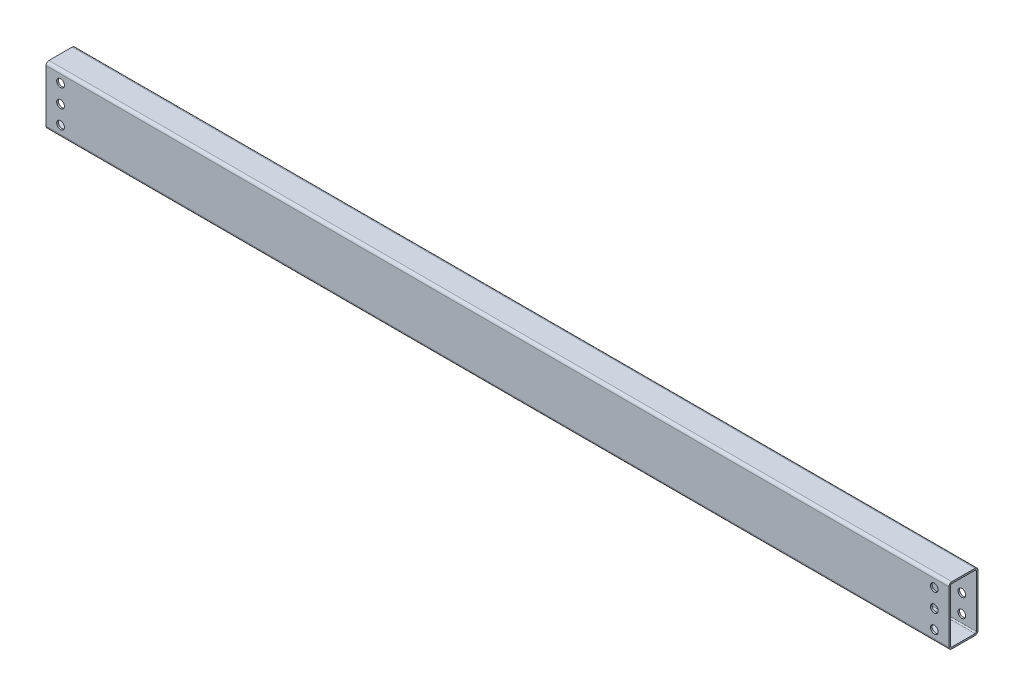
SolidWorks part; units mm, degrees
material "6061-T6 (SS)"
ref_plane "Front" through (0, 0, 0) normal (0, 0, 1) x (1, 0, 0)
ref_plane "Top" through (0, 0, 0) normal (0, 1, 0) x (1, 0, 0)
ref_plane "Right" through (0, 0, 0) normal (1, 0, 0) x (0, 0, -1)
sketch "Sketch1" plane through (0, 0, 0) normal (1, 0, 0) x (0, 0, -1)
  line L0 (10.16, -25.4) -> (-10.16, -25.4)
  line L1 (12.7, -22.86) -> (12.7, 22.86)
  line L2 (10.16, 25.4) -> (-10.16, 25.4)
  line L3 (-12.7, -22.86) -> (-12.7, 22.86)
  line L4 (12.7, -25.4) -> (-12.7, 25.4) construction
  line L5 (12.7, 25.4) -> (-12.7, -25.4) construction
  arc A0 (-10.16, -25.4) -> (-12.7, -22.86) centre (-10.16, -22.86) cw
  arc A1 (10.16, -25.4) -> (12.7, -22.86) centre (10.16, -22.86) ccw
  arc A2 (12.7, 22.86) -> (10.16, 25.4) centre (10.16, 22.86) ccw
  arc A3 (-10.16, 25.4) -> (-12.7, 22.86) centre (-10.16, 22.86) ccw
  point P0 (0, 0)
  dimension "D3" = 2.54
  dimension "D1" = 25.4
  dimension "D2" = 50.8
extrude "Extrude-Thin1" add sketch "Sketch1" along normal mid plane 787.4 thin thin type one direction reverse wall 1.4478
hole_wizard "1/4 Clearance Hole1" positions "Sketch2" profile "Sketch3" hole size "1/4" standard "ANSI Inch" end condition through all
sketch "Sketch2" plane through (0, 0, -12.7) normal (0, 0, -1) x (-1, 0, 0)
  line L0 (-393.7, -22.86) -> (-393.7, 22.86) construction
  line L1 (-393.7, 25.4) -> (393.7, 25.4) construction
  line L2 (-393.7, -25.4) -> (393.7, -25.4) construction
  line L3 (-381, 15.875) -> (-381, -15.875) construction
  line L4 (0, 0) -> (0, -37.3791) construction
  point P0 (-381, 15.875)
  point P2 (-381, -15.875)
  point P15 (-381, 0)
  point P23 (381, -15.875)
  point P24 (381, 0)
  point P25 (381, 15.875)
  dimension "D1" = 12.7
  dimension "D2" = 9.525
  dimension "D3" = 9.525
sketch "Sketch3" plane through (381, 15.875, -12.7) normal (1, 0, 0) x (0, 1, 0)
  line L0 (0, 0) -> (0, 25.4)
  line L1 (0, 25.4) -> (3.3782, 25.4)
  line L2 (3.3782, 25.4) -> (3.3782, 0)
  line L5 (3.3782, 0) -> (0, 0)
  line L11 (0, -6.35) -> (0, 107.95) construction
  dimension "Thru Hole Dia." = 6.7564
  dimension "Thru Hole Depth" = 25.4
hole_wizard "1/4 Clearance Hole2" positions "Sketch4" profile "Sketch5" hole size "1/4" standard "ANSI Inch" end condition up to next
sketch "Sketch4" plane through (0, 0, -12.7) normal (0, 0, -1) x (-1, 0, 0)
  line L0 (-234.95, 15.875) -> (-234.95, -15.875) construction
  line L2 (-393.7, 25.4) -> (393.7, 25.4) construction
  line L3 (-393.7, -25.4) -> (393.7, -25.4) construction
  line L4 (0, 0) -> (0, -51.4899) construction
  point P19 (-234.95, 15.875)
  point P21 (-234.95, 0)
  point P23 (-234.95, -15.875)
  point P42 (234.95, -15.875)
  point P43 (234.95, 0)
  point P44 (234.95, 15.875)
  dimension "D1" = 9.525
  dimension "D2" = 9.525
  dimension "D3" = 469.9
sketch "Sketch5" plane through (234.95, 15.875, -12.7) normal (1, 0, 0) x (0, 1, 0)
  line L0 (0, 0) -> (0, 1.4478)
  line L1 (0, 1.4478) -> (3.3782, 1.4478)
  line L2 (3.3782, 1.4478) -> (3.3782, 0)
  line L5 (3.3782, 0) -> (0, 0)
  line L11 (0, -6.35) -> (0, 107.95) construction
  dimension "Thru Hole Dia." = 6.7564
  dimension "Thru Hole Depth" = 1.4478
